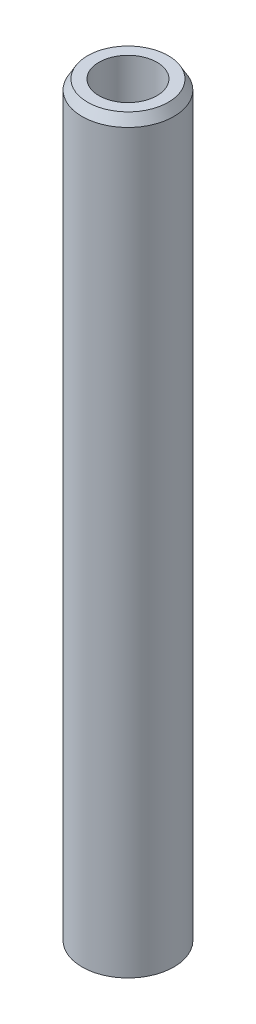
SolidWorks part; units mm, degrees
ref_plane "Front Plane" through (0, 0, 0) normal (0, 0, 1) x (1, 0, 0)
ref_plane "Top Plane" through (0, 0, 0) normal (0, 1, 0) x (1, 0, 0)
ref_plane "Right Plane" through (0, 0, 0) normal (1, 0, 0) x (0, 0, -1)
sketch "Sketch1" plane through (0, 0, 0) normal (0, 1, 0) x (1, 0, 0)
  circle A0 centre (0, 0) radius 20
  dimension "SHAFT_OD" = 40
extrude "Boss-Extrude1" add sketch "Sketch1" along normal blind 327.5463
sketch "Sketch2" plane through (0, 0, 0) normal (0, 1, 0) x (1, 0, 0)
  circle A0 centre (0, 0) radius 12.6396
  dimension "BORE_D" = 25.2792
extrude "Cut-Extrude1" cut sketch "Sketch2" along normal through all
chamfer "Chamfer1" distance 4.1788 angle 30 2 edges at (0, 327.5463, 20) (0, 0, 20) first distance on face at (0, 327.5463, 20) first distance on face at (0, 0, 12.6396)
